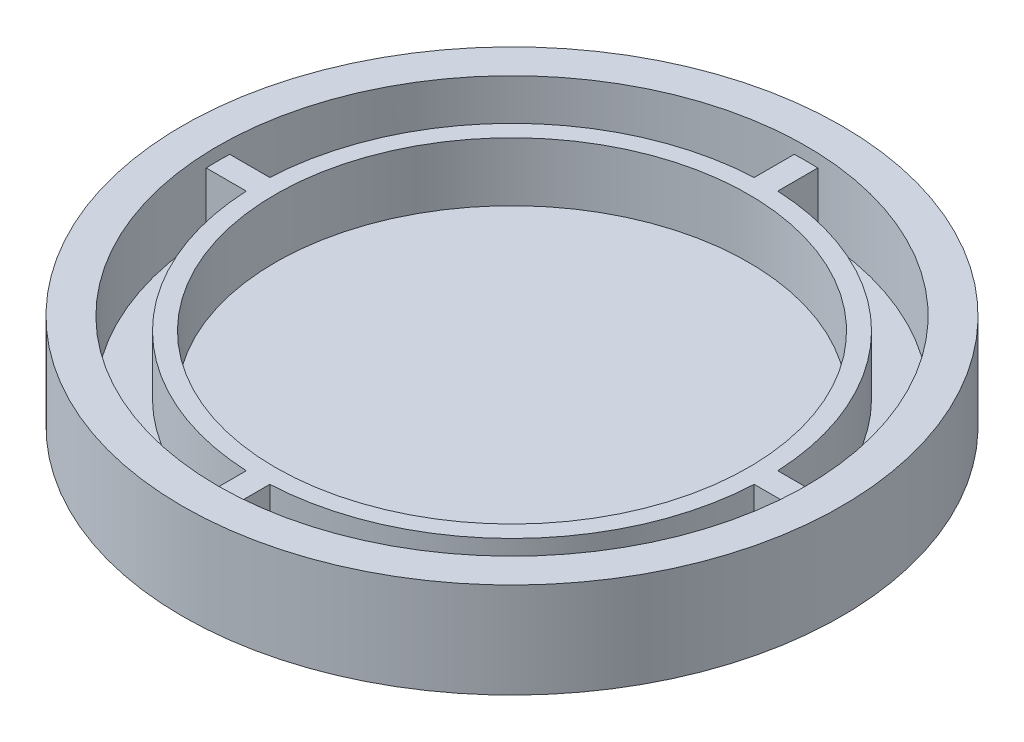
SolidWorks part; units mm, degrees
ref_plane "Front Plane" through (0, 0, 0) normal (0, 0, 1) x (1, 0, 0)
ref_plane "Top Plane" through (0, 0, 0) normal (0, 1, 0) x (1, 0, 0)
ref_plane "Right Plane" through (0, 0, 0) normal (1, 0, 0) x (0, 0, -1)
sketch "Sketch1" plane through (0, 0, 0) normal (0, 1, 0) x (1, 0, 0)
  circle A0 centre (0, 0) radius 20.1
  circle A1 centre (0, 0) radius 28
  circle A2 centre (0, 0) radius 25
  circle A3 centre (0, 0) radius 21.6
extrude "Boss-Extrude1" add sketch "Sketch1" along normal blind 8 contours A1 | A2
extrude "Boss-Extrude2" add sketch "Sketch1<3>" against normal blind 2 contours A1
sketch "Sketch1<3>" plane through (0, 0, 0) normal (0, 1, 0) x (1, 0, 0) same geometry as "Sketch1"
extrude "Boss-Extrude3" add sketch "Sketch1<5>" along normal blind 5 contours A3 | A0
sketch "Sketch1<5>" plane through (0, 0, 0) normal (0, 1, 0) x (1, 0, 0) same geometry as "Sketch1"
sketch "Sketch5" plane through (0, 8, 0) normal (0, 1, 0) x (1, 0, 0)
  circle A0 centre (0, 0) radius 28
extrude "Cut-Extrude1" cut sketch "Sketch5" against normal blind 1.9
sketch "Sketch10" plane through (0, 0, 0) normal (0, 1, 0) x (1, 0, 0)
  line L0 (1, -21.5768) -> (1, -25)
  line L1 (-21.5768, 1) -> (-25, 1)
  line L2 (-21.5768, -1) -> (-25, -1)
  line L3 (21.5768, -1) -> (25, -1)
  line L4 (21.5768, 1) -> (25, 1)
  line L5 (-25, 1) -> (-25, -1)
  line L6 (1, 21.5768) -> (1, 25)
  line L7 (-1, 21.5768) -> (-1, 25)
  line L8 (-1, -21.5768) -> (-1, -25)
  line L9 (-21.5768, 1) -> (-21.5768, -1)
  line L10 (-1, 25) -> (1, 25)
  line L11 (-1, 21.5768) -> (1, 21.5768)
  line L12 (21.5768, 1) -> (21.5768, -1)
  line L13 (25, 1) -> (25, -1)
  line L14 (-1, -21.5768) -> (1, -21.5768)
  line L15 (-1, -25) -> (1, -25)
extrude "Boss-Extrude4" add sketch "Sketch10" along normal up to surface (5 mm away) up to face at (0, 5, 21.6)
